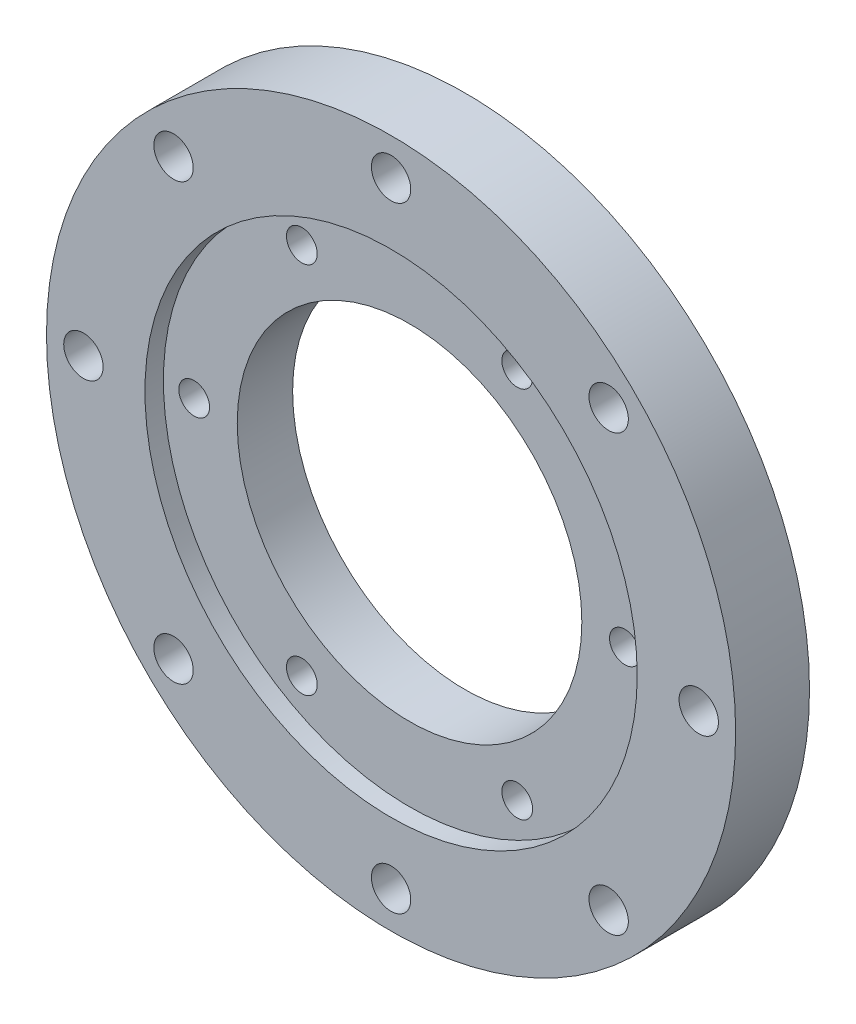
SolidWorks part; units mm, degrees
note: The reader was unsure of these and kept them because the rebuilt part matched: shared geometry of "ｽｹｯﾁ1<4>".
material "3.1325 (EN-AW 2017A)"
ref_plane "正面" through (0, 0, 0) normal (0, 0, 1) x (1, 0, 0)
ref_plane "平面" through (0, 0, 0) normal (0, 1, 0) x (1, 0, 0)
ref_plane "右側面" through (0, 0, 0) normal (1, 0, 0) x (0, 0, -1)
sketch "ｽｹｯﾁ1" plane through (0, 0, 0) normal (0, 0, 1) x (1, 0, 0)
  circle A0 centre (0, 0) radius 14
  circle A1 centre (0, 0) radius 20
  circle A2 centre (0, 0) radius 28
  circle A3 centre (0, 0) radius 17.5 construction
  circle A4 centre (0, 0) radius 25 construction
  point P7 (17.5, 0)
  point P8 (0, 25)
  point P12 (17.6777, 17.6777)
  point P13 (25, 0)
  point P14 (17.6777, -17.6777)
  point P15 (0, -25)
  point P16 (-17.6777, -17.6777)
  point P17 (-25, 0)
  point P18 (-17.6777, 17.6777)
  point P19 (0, 0)
  point P20 (8.75, -15.1554)
  point P21 (-8.75, -15.1554)
  point P22 (-17.5, 0)
  point P23 (-8.75, 15.1554)
  point P24 (8.75, 15.1554)
  point P25 (0, 0)
  dimension "D1" = 28
  dimension "D2" = 40
  dimension "D3" = 56
  dimension "D4" = 35
  dimension "D5" = 50
  dimension "D6" = 8
  dimension "D7" = 6
extrude "ﾎﾞｽ - 押し出し1" add sketch "ｽｹｯﾁ1" along normal blind 6 contours A2 | A0
extrude "ｶｯﾄ - 押し出し1" cut sketch "ｽｹｯﾁ1<4>" against normal blind 1.5 from surface at 6 contours A1 | A0 starting at face at (28, 0, 6)
sketch "ｽｹｯﾁ1<4>" plane through (0, 0, 0) normal (0, 0, 1) x (1, 0, 0) same geometry as "ｽｹｯﾁ1"
hole_wizard "M3x0.5 ねじ穴用ねじ下穴ﾄﾞﾘﾙ1" positions "3Dｽｹｯﾁ3" profile "ｽｹｯﾁ2" hole size "M3x0.5" standard "JIS" end condition through all
sketch3d "3Dｽｹｯﾁ3"
  point P0 (17.5, 0, 0)
  point P2 (8.75, -15.1554, 0)
  point P4 (-8.75, -15.1554, 0)
  point P6 (-17.5, 0, 0)
  point P8 (-8.75, 15.1554, 0)
  point P10 (8.75, 15.1554, 0)
sketch "ｽｹｯﾁ2" plane through (17.5, 0, 0) normal (1, 0, 0) x (0, 1, 0)
  line L0 (0, 0) -> (0, 6)
  line L1 (0, 6) -> (1.25, 6)
  line L2 (1.25, 6) -> (1.25, 0)
  line L5 (1.25, 0) -> (0, 0)
  line L11 (0, -6.35) -> (0, 107.95) construction
  dimension "通し穴の直径" = 2.5
  dimension "通し穴の深さ" = 6
hole_wizard "M3x0.5 ねじ穴用ねじ下穴ﾄﾞﾘﾙ2" [suppressed] positions "3Dｽｹｯﾁ4" profile "ｽｹｯﾁ3" hole size "M3x0.5" standard "JIS"
sketch3d "3Dｽｹｯﾁ4"
  point P0 (9.5671, 23.097, 0)
  point P2 (23.097, 9.5671, 0)
  point P4 (23.097, -9.5671, 0)
  point P6 (9.5671, -23.097, 0)
  point P8 (-9.5671, -23.097, 0)
  point P10 (-23.097, -9.5671, 0)
  point P12 (-23.097, 9.5671, 0)
  point P14 (-9.5671, 23.097, 0)
sketch "ｽｹｯﾁ3" plane through (9.5671, 23.097, 0) normal (1, 0, 0) x (0, 1, 0)
  line L0 (0, 0) -> (0, 6)
  line L1 (0, 6) -> (1.25, 6)
  line L2 (1.25, 6) -> (1.25, 0)
  line L5 (1.25, 0) -> (0, 0)
  line L11 (0, -6.35) -> (0, 107.95) construction
  dimension "通し穴の直径" = 2.5
  dimension "通し穴の深さ" = 6
hole_wizard "M3 すきま穴1" positions "3Dｽｹｯﾁ5" profile "ｽｹｯﾁ4" hole size "M3" standard "JIS" end condition through all
sketch3d "3Dｽｹｯﾁ5"
  point P0 (0, 25, 0)
  point P2 (17.6777, 17.6777, 0)
  point P4 (25, 0, 0)
  point P6 (17.6777, -17.6777, 0)
  point P8 (0, -25, 0)
  point P10 (-17.6777, -17.6777, 0)
  point P12 (-25, 0, 0)
  point P14 (-17.6777, 17.6777, 0)
sketch "ｽｹｯﾁ4" plane through (0, 25, 0) normal (1, 0, 0) x (0, 1, 0)
  line L0 (0, 0) -> (0, 6)
  line L1 (0, 6) -> (1.6, 6)
  line L2 (1.6, 6) -> (1.6, 0)
  line L5 (1.6, 0) -> (0, 0)
  line L11 (0, -6.35) -> (0, 107.95) construction
  dimension "通し穴の直径" = 3.2
  dimension "通し穴の深さ" = 6
